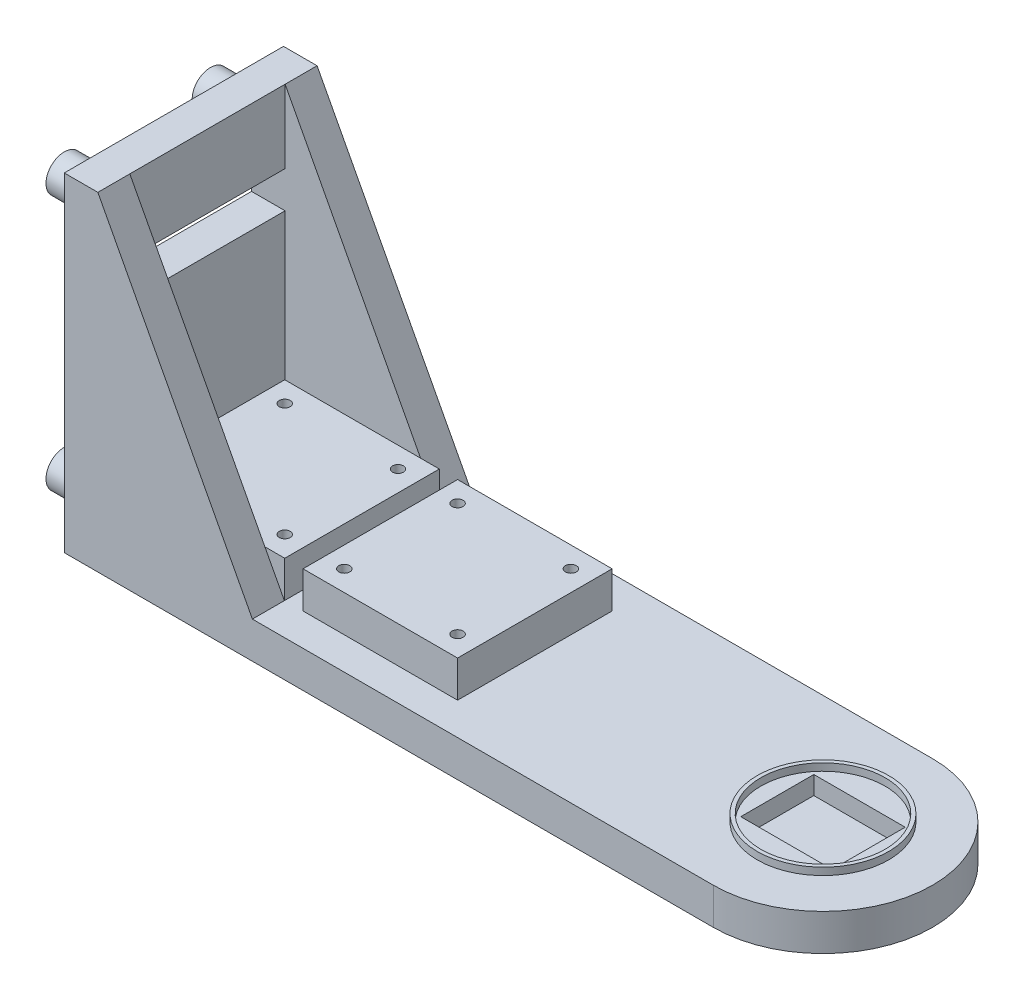
SolidWorks part; units mm, degrees
ref_plane "Front Plane" through (0, 0, 0) normal (0, 0, 1) x (1, 0, 0)
ref_plane "Top Plane" through (0, 0, 0) normal (0, 1, 0) x (1, 0, 0)
ref_plane "Right Plane" through (0, 0, 0) normal (1, 0, 0) x (0, 0, -1)
sketch "Sketch2" plane through (0, 0, 0) normal (0, 1, 0) x (1, 0, 0)
  line L0 (-7.6378, -30) -> (100, -30)
  line L1 (-15.5, 15.5) -> (15.5, 15.5) construction
  line L2 (-15.5, 15.5) -> (-15.5, -15.5) construction
  line L3 (-15.5, -15.5) -> (15.5, -15.5) construction
  line L4 (15.5, 15.5) -> (15.5, -15.5) construction
  line L5 (-15.5, 15.5) -> (15.5, -15.5) construction
  line L6 (-15.5, -15.5) -> (15.5, 15.5) construction
  line L7 (-21.15, 21.15) -> (21.15, 21.15)
  line L8 (-21.15, 21.15) -> (-21.15, -21.15)
  line L9 (-21.15, -21.15) -> (21.15, -21.15)
  line L10 (21.15, 21.15) -> (21.15, -21.15)
  line L11 (-21.15, 21.15) -> (21.15, -21.15) construction
  line L12 (-21.15, -21.15) -> (21.15, 21.15) construction
  line L13 (-7.6378, 30) -> (100, 30)
  line L14 (-21.15, -21.15) -> (-24.6855, -24.6855) construction
  line L15 (121.15, 21.2762) -> (121.15, -21.2762)
  line L16 (-7.6378, -30) -> (-37.6378, -30)
  line L17 (-37.6378, -30) -> (-37.6378, 30)
  line L18 (-37.6378, 30) -> (-7.6378, 30)
  line L19 (0, 0) -> (100, 0) construction
  circle A0 centre (-15.5, 15.5) radius 1.5
  circle A1 centre (15.5, 15.5) radius 1.5
  circle A2 centre (15.5, -15.5) radius 1.5
  circle A3 centre (-15.5, -15.5) radius 1.5
  arc A5 (-7.6378, 30) -> (-7.6378, -30) centre (-7.6378, 0) ccw
  arc A6 (100, 30) -> (100, -30) centre (100, 0) cw
  point P0 (0, 0)
  point P10 (0, 0)
  dimension "D3" = 3
  dimension "D5" = 60
  dimension "D9" = 30
  dimension "D1" = 31
  dimension "D2" = 31
  dimension "D4" = 42.3
  dimension "D6" = 5
  dimension "D7" = 100
  dimension "D8" = 100
extrude "Boss-Extrude1" add sketch "Sketch2" along normal blind 10 contours L13 A5 L0 L15 L7 L10 L9 L8 | L10 L7 L8 L9 A3 A2 A1 A0 | A5 L17 L16 | A5 L18 L17 | A6 L15 | L15 L0 A5 L13 region at (54.7818, 0, 0) region at (-30.9368, 0, 23.299) region at (-30.9368, 0, -23.299) region at (124.739, 0, 0) region at (0, 0, 0)
sketch "Sketch3" plane through (0, 10, 0) normal (0, 1, 0) x (1, 0, 0)
  line L0 (0, 0) -> (100, 0) construction
  line L1 (-15.5, 15.5) -> (15.5, -15.5) construction
  line L3 (87.5, 10) -> (112.5, 10)
  line L4 (87.5, 10) -> (87.5, -10)
  line L5 (87.5, -10) -> (112.5, -10)
  line L6 (112.5, 10) -> (112.5, -10)
  line L7 (87.5, 10) -> (112.5, -10) construction
  line L8 (87.5, -10) -> (112.5, 10) construction
  dimension "D1" = 100
  dimension "D2" = 25
  dimension "D3" = 20
extrude "Cut-Extrude1" cut sketch "Sketch3" against normal blind 5
sketch "Sketch5" plane through (0, 10, 0) normal (0, 1, 0) x (1, 0, 0)
  line L0 (87.5, 0) -> (112.5, 0) construction
  line L1 (100, -10) -> (100, 10) construction
  line L4 (112.5, -10) -> (112.5, 10)
  line L5 (112.5, 10) -> (87.5, 10)
  line L6 (87.5, 10) -> (87.5, -10)
  line L7 (87.5, -10) -> (112.5, -10)
  line L8 (112.5, -10) -> (112.5, 10) construction
  line L9 (112.5, 10) -> (87.5, 10) construction
  line L10 (87.5, 10) -> (87.5, -10) construction
  line L11 (87.5, -10) -> (112.5, -10) construction
  circle A0 centre (100, 0) radius 17
  circle A1 centre (100, 0) radius 18
  dimension "D3" = 34
  dimension "D1" = 0
  dimension "D2" = 1
extrude "Boss-Extrude2" add sketch "Sketch5" along normal blind 2
extrude "Boss-Extrude3" add sketch "Sketch2<3>" along normal blind 20 contours L10 L7 L8 L9 A3 A2 A1 A0 region at (0, 0, 0)
sketch "Sketch2<3>" plane through (0, 0, 0) normal (0, 1, 0) x (1, 0, 0) same geometry as "Sketch2"
sketch "Sketch6" plane through (0, 10, 0) normal (0, 1, 0) x (1, 0, 0)
  line L0 (-21.15, 21.15) -> (21.15, 21.15) construction
  line L1 (-21.15, -21.15) -> (-26.15, -21.15)
  line L2 (-21.15, -21.15) -> (-21.15, 21.15)
  line L3 (-21.15, 21.15) -> (-26.15, 21.15)
  line L4 (-26.15, -21.15) -> (-26.15, 21.15)
  dimension "D1" = 5
sketch "Sketch8" plane through (0, 0, 0) normal (0, -1, 0) x (1, 0, 0)
  line L0 (-37.6378, -30) -> (-7.6378, -30) construction
  line L1 (-77.6378, -30) -> (-37.6378, -30)
  line L2 (-77.6378, -30) -> (-77.6378, 30)
  line L3 (-77.6378, 30) -> (-37.6378, 30)
  line L4 (-37.6378, -30) -> (-37.6378, 30)
  line L5 (-77.6378, -30) -> (-37.6378, 30) construction
  line L6 (-77.6378, 30) -> (-37.6378, -30) construction
  point P0 (-57.6378, 0)
  dimension "D1" = 40
extrude "Boss-Extrude4" add sketch "Sketch8" against normal blind 10
sketch "Sketch9" plane through (0, 10, 0) normal (0, 1, 0) x (1, 0, 0)
  line L1 (-68.45, 21.15) -> (-26.15, 21.15)
  line L2 (-68.45, 21.15) -> (-68.45, -21.15)
  line L3 (-68.45, -21.15) -> (-26.15, -21.15)
  line L4 (-26.15, 21.15) -> (-26.15, -21.15)
  line L5 (-68.45, 21.15) -> (-26.15, -21.15) construction
  line L6 (-68.45, -21.15) -> (-26.15, 21.15) construction
  circle A0 centre (-31.8, 15.5) radius 1.5
  circle A1 centre (-31.8, -15.5) radius 1.5
  circle A2 centre (-62.8, -15.5) radius 1.5
  circle A3 centre (-62.8, 15.5) radius 1.5
  point P0 (-47.3, 0)
  point P15 (0, 0)
  point P16 (0, 0)
  point P17 (0, 0)
  point P18 (0, 0)
  point P19 (-59.3504, -12.0504)
  point P20 (0, 0)
  point P21 (0, 0)
  point P22 (-57.897, -10.597)
  point P23 (0, 0)
  point P24 (0, 0)
  point P25 (0, 0)
  point P26 (0, 0)
  point P27 (-59.1661, -11.8661)
  dimension "D2" = 3
  dimension "D1" = 42.3
  dimension "D3" = 31
extrude "Boss-Extrude5" add sketch "Sketch9" along normal blind 10
extrude "Cut-Extrude3" cut sketch "Sketch9<3>" against normal blind 10 contours A2 | A1 | A0 | A3 region at (-31.8, 10, -15.5) region at (-31.8, 10, 15.5) region at (-62.8, 10, 15.5) region at (-62.8, 10, -15.5)
sketch "Sketch9<3>" plane through (0, 10, 0) normal (0, 1, 0) x (1, 0, 0) same geometry as "Sketch9"
sketch "Sketch10" plane through (0, 10, 0) normal (0, 1, 0) x (1, 0, 0)
  line L0 (-77.6378, -30) -> (100, -30) construction
  line L1 (-77.6378, 30) -> (-68.45, 30)
  line L2 (-77.6378, 30) -> (-77.6378, -30)
  line L3 (-77.6378, -30) -> (-68.45, -30)
  line L4 (-68.45, 30) -> (-68.45, -30)
  line L5 (-68.45, 21.15) -> (-68.45, -21.15) construction
extrude "Boss-Extrude6" add sketch "Sketch10" along normal blind 80
sketch "Sketch11" plane through (-77.6378, 0, 0) normal (-1, 0, 0) x (0, 0, 1)
  line L0 (-20, 10) -> (20, 10)
  line L1 (20, 10) -> (20, 80)
  line L2 (20, 80) -> (-20, 80)
  line L3 (-20, 80) -> (-20, 10)
  line L4 (-30, 0) -> (30, 0)
  line L5 (30, 0) -> (30, 90)
  line L6 (30, 90) -> (-30, 90)
  line L7 (-30, 90) -> (-30, 0)
  line L8 (-30, 0) -> (30, 0)
  line L9 (30, 0) -> (30, 90)
  line L10 (30, 90) -> (-30, 90)
  line L11 (-30, 90) -> (-30, 0)
  circle A0 centre (-20, 80) radius 5
  circle A1 centre (20, 80) radius 5
  circle A2 centre (20, 10) radius 5
  circle A3 centre (-20, 10) radius 5
  circle A4 centre (-20, 10) radius 7.5
  circle A5 centre (-20, 80) radius 7.5
  circle A6 centre (20, 80) radius 7.5
  circle A7 centre (20, 10) radius 7.5
  dimension "D3" = 10
  dimension "D4" = 10
  dimension "D5" = 10
  dimension "D6" = 10
  dimension "D1" = 0
  dimension "D2" = 10
  dimension "D7" = 2.5
sketch "Sketch13" plane through (0, 0, 30) normal (0, 0, 1) x (1, 0, 0)
  line L0 (-68.45, 90) -> (-26.15, 10)
  line L1 (-26.15, 10) -> (-68.45, 10)
  line L2 (-68.45, 10) -> (-68.45, 90)
extrude "Boss-Extrude7" add sketch "Sketch13" against normal blind 8.75
mirror "Mirror2" about plane through (0, 0, 0) normal (0, 0, 1) of "Boss-Extrude7"
extrude "Boss-Extrude9" add sketch "Sketch11" along normal blind 10 contours L2 A0 L3 | L3 A0 L2 | L1 A1 L2 | L2 A1 L1 | L0 A2 L1 | L1 A2 L0 | L3 A3 L0 | L0 A3 L3 region at (-77.6378, 12.1221, -17.8779) region at (-77.6378, 9.2926, -20.7074) region at (-77.6378, 12.1221, 17.8779) region at (-77.6378, 9.2926, 20.7074) region at (-77.6378, 80.7074, -20.7074) region at (-77.6378, 77.8779, -17.8779) region at (-77.6378, 77.8779, 17.8779) region at (-77.6378, 80.7074, 20.7074)
sketch "Sketch16" plane through (-68.45, 0, 0) normal (1, 0, 0) x (0, 0, -1)
  line L0 (-21.25, 90) -> (-21.25, 70) construction
  line L1 (-21.25, 10) -> (-21.25, 90) construction
  line L2 (21.25, 90) -> (21.25, 10) construction
  line L3 (-21.25, 70) -> (21.25, 70)
  line L4 (-21.25, 70) -> (-21.25, 60)
  line L5 (-21.25, 60) -> (21.25, 60)
  line L6 (21.25, 70) -> (21.25, 60)
  dimension "D1" = 20
  dimension "D2" = 10
extrude "Cut-Extrude5" cut sketch "Sketch16" against normal up to surface (9.1878 mm away) up to face at (-77.6378, 10, -15)
